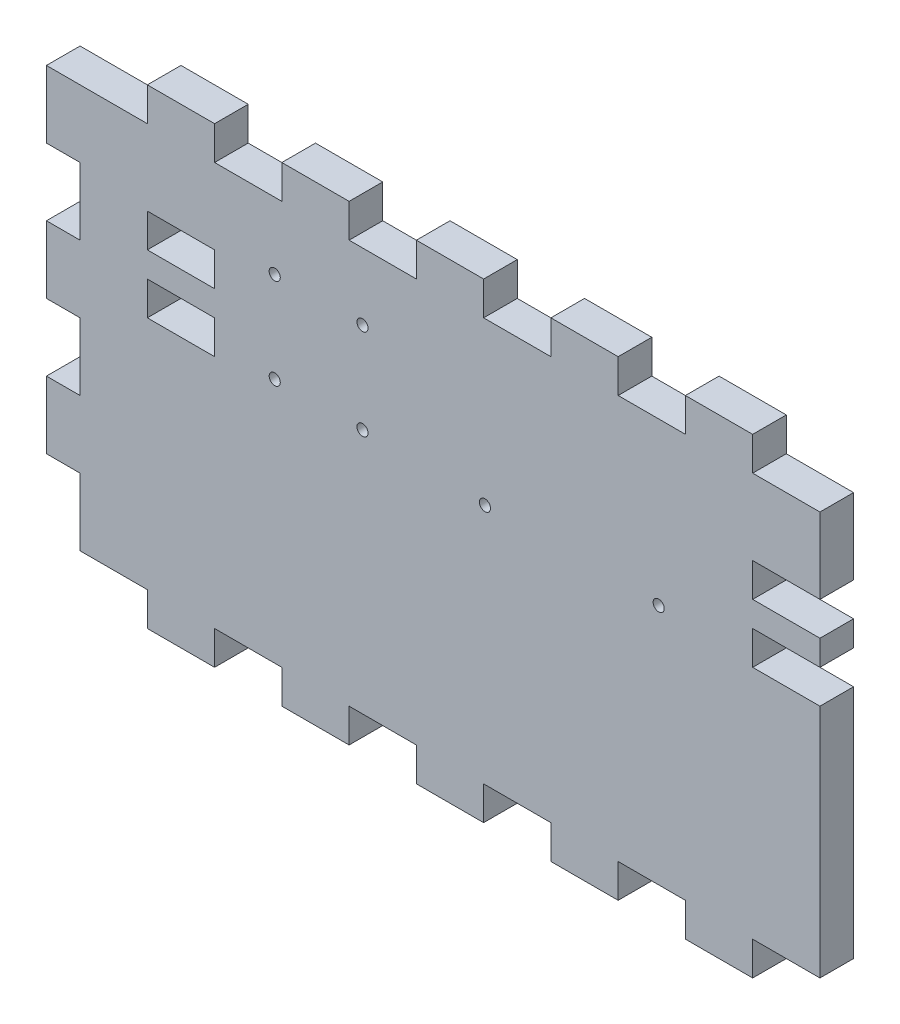
SolidWorks part; units mm, degrees
ref_plane "Front Plane" through (0, 0, 0) normal (0, 0, 1) x (1, 0, 0)
ref_plane "Top Plane" through (0, 0, 0) normal (0, 1, 0) x (1, 0, 0)
ref_plane "Right Plane" through (0, 0, 0) normal (1, 0, 0) x (0, 0, -1)
sketch "Sketch1" plane through (0, 0, 0) normal (0, 0, 1) x (1, 0, 0)
  line L1 (-139.7, -76.2) -> (139.7, -76.2)
  line L2 (-139.7, -76.2) -> (-139.7, 76.2)
  line L3 (-139.7, 76.2) -> (139.7, 76.2)
  line L4 (139.7, -76.2) -> (139.7, 76.2)
  line L5 (-139.7, -76.2) -> (139.7, 76.2) construction
  line L6 (-139.7, 76.2) -> (139.7, -76.2) construction
  point P0 (0, 0)
  dimension "D1" = 279.4
  dimension "D2" = 152.4
extrude "Boss-Extrude1" add sketch "Sketch1" along normal blind 12.7
sketch "Sketch2" plane through (0, -76.2, 0) normal (0, -1, 0) x (1, 0, 0)
  line L0 (-139.7, 0) -> (139.7, 0) construction
  line L1 (-114.3, 0) -> (-88.9, 0)
  line L2 (-114.3, 0) -> (-114.3, 12.7)
  line L3 (-114.3, 12.7) -> (-88.9, 12.7)
  line L4 (-88.9, 0) -> (-88.9, 12.7)
  line L5 (-139.7, 12.7) -> (139.7, 12.7) construction
  line L6 (-139.7, 12.7) -> (-139.7, 0) construction
  point P10 (-139.7, 6.35)
  dimension "D1" = 25.4
  dimension "D2" = 25.4
extrude "Boss-Extrude2" add sketch "Sketch2" along normal blind 12.7
pattern_linear "LPattern1" count 5 spacing 50.8 along (1, 0, 0) of "Boss-Extrude2"
mirror "Mirror1" about plane through (0, 0, 0) normal (0, 1, 0) of "LPattern1"
sketch "Sketch3" plane through (-139.7, 0, 0) normal (-1, 0, 0) x (0, 0, 1)
  line L0 (0, 76.2) -> (0, -76.2) construction
  line L1 (12.7, 76.2) -> (0, 76.2)
  line L2 (12.7, 76.2) -> (12.7, 50.8)
  line L3 (12.7, 50.8) -> (0, 50.8)
  line L4 (0, 76.2) -> (0, 50.8)
  dimension "D1" = 25.4
extrude "Boss-Extrude3" add sketch "Sketch3" along normal blind 12.7
pattern_linear "LPattern2" count 3 spacing 50.8 along (0, -1, 0) of "Boss-Extrude3"
sketch "Sketch4" plane through (0, 0, 0) normal (0, 0, -1) x (-1, 0, 0)
  line L1 (-139.7, 12.7) -> (-114.3, 12.7)
  line L2 (-139.7, 12.7) -> (-139.7, 25.4)
  line L3 (-139.7, 25.4) -> (-114.3, 25.4)
  line L4 (-114.3, 12.7) -> (-114.3, 25.4)
  line L5 (-114.3, -76.2) -> (-139.7, -76.2) construction
  line L6 (-139.7, -76.2) -> (-139.7, 76.2) construction
  dimension "D1" = 25.4
  dimension "D2" = 12.7
  dimension "D4" = 88.9
extrude "Cut-Extrude1" cut sketch "Sketch4" against normal through all
pattern_linear "LPattern3" count 2 spacing 228.6 along (-1, 0, 0) of "Cut-Extrude1"
sketch "Sketch5" plane through (0, 0, 12.7) normal (0, 0, 1) x (1, 0, 0)
  line L0 (-139.7, -76.2) -> (-114.3, -76.2) construction
  line L1 (-88.9, 47.625) -> (-114.3, 47.625)
  line L2 (-88.9, 47.625) -> (-88.9, 34.925)
  line L3 (-88.9, 34.925) -> (-114.3, 34.925)
  line L4 (-114.3, 47.625) -> (-114.3, 34.925)
  line L8 (-114.3, 12.7) -> (-114.3, 25.4) construction
  dimension "D1" = 25.4
  dimension "D2" = 12.7
  dimension "D3" = 123.825
extrude "Cut-Extrude2" cut sketch "Sketch5" against normal through all
pattern_linear "LPattern4" count 2 spacing 228.6 along (1, 0, 0) of "Cut-Extrude2"
sketch "Sketch6" plane through (0, 0, 0) normal (0, 0, -1) x (-1, 0, 0)
  circle A0 centre (-78.8111, 15.175) radius 2.1 construction
  circle A1 centre (-78.8111, 15.175) radius 2.1
  circle A2 centre (-13.2039, 15.175) radius 2.1 construction
  circle A3 centre (-13.2039, 15.175) radius 2.1
  circle A4 centre (66.195, 16.6838) radius 2.1 construction
  circle A5 centre (66.195, 16.6838) radius 2.1
  circle A6 centre (33.045, 50.945) radius 2.1 construction
  circle A7 centre (33.045, 50.945) radius 2.1
  circle A8 centre (66.195, 50.945) radius 2.1 construction
  circle A9 centre (66.195, 50.945) radius 2.1
  circle A10 centre (33.045, 16.6838) radius 2.1 construction
  circle A11 centre (33.045, 16.6838) radius 2.1
extrude "Cut-Extrude3" cut sketch "Sketch6" against normal through all
